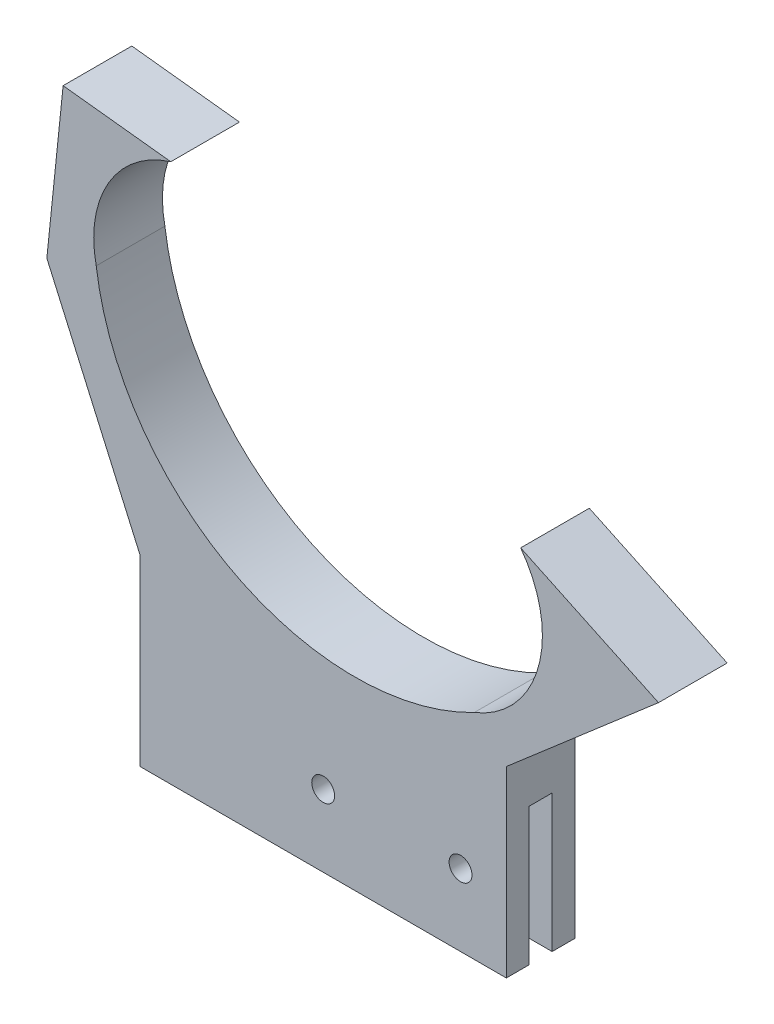
SolidWorks part; units mm, degrees
other "Markup1"
sketch "Sketch6" plane through (114.3, 38.1, 139.7) normal (0.0122, 0.8279, 0.5607) x (0.9984, -0.0412, 0.0392)
material "Balsa"
ref_plane "Front Plane" through (0, 0, 0) normal (0, 0, 1) x (1, 0, 0)
ref_plane "Top Plane" through (0, 0, 0) normal (0, 1, 0) x (1, 0, 0)
ref_plane "Right Plane" through (0, 0, 0) normal (1, 0, 0) x (0, 0, -1)
sketch "Sketch7" plane through (0, 0, 0) normal (0, 0, 1) x (1, 0, 0)
  line L1 (0, 0) -> (50.8, 0)
  line L2 (0, 0) -> (0, 19.05)
  line L3 (0, 19.05) -> (50.8, 19.05)
  line L4 (50.8, 0) -> (50.8, 19.05)
  circle A0 centre (25.4, 9.9757) radius 1.5875
  circle A1 centre (44.45, 9.9757) radius 1.5875
  point P9 (0, 0)
  dimension "Mount Diameter" = 3.175
  dimension "Mount Width" = 19.05
  dimension "Mount Length" = 50.8
  dimension "Basket Mount" = 19.05
  dimension "Mount Offset" = 6.35
extrude "Boss-Extrude1" add sketch "Sketch7" along normal mid plane 9.525 contours L3 L4 L1 L2 | A0 | A1
extrude "Cut-Extrude1" cut sketch "Sketch7<6>" against normal mid plane 3.175 contours L3 L4 L1 L2
sketch "Sketch7<6>" plane through (0, 0, 0) normal (0, 0, 1) x (1, 0, 0) same geometry as "Sketch7"
sketch "Sketch13" plane through (0, 0, 4.7625) normal (0, 0, 1) x (1, 0, 0)
  line L0 (0, 19.05) -> (50.8, 19.05)
  line L1 (0, 19.05) -> (0, 25.4)
  line L2 (50.8, 19.05) -> (50.8, 25.4)
  line L3 (0, 25.4) -> (50.8, 25.4)
  dimension "D1" = 6.35
extrude "Boss-Extrude4" add sketch "Sketch13" against normal blind 9.525
sketch "Sketch14" plane through (0, 0, 4.7625) normal (0, 0, 1) x (1, 0, 0)
  line L0 (50.8, 25.4) -> (71.9025, 43.6226)
  line L1 (71.9025, 43.6226) -> (52.7873, 52.6559)
  line L2 (0, 25.4) -> (-12.9266, 54.5938)
  line L4 (0, 25.4) -> (50.8, 25.4)
  line L5 (4.2644, 74.7738) -> (-10.6693, 76.4461)
  line L6 (-10.6693, 76.4461) -> (-12.9266, 54.5938)
  arc A0 (-6.0786, 57.1043) -> (46.3569, 29.6648) centre (29.7863, 61.8197) ccw
  arc A1 (46.3569, 29.6648) -> (52.7873, 52.6559) centre (40.7687, 43.6226) ccw
  arc A2 (-6.0786, 57.1043) -> (4.2644, 74.7738) centre (8.7052, 60.3125) cw
extrude "Boss-Extrude5" add sketch "Sketch14" against normal blind 9.525
equation "\"L1\"= 15in"
equation "\"L2\"= 12.5in"
equation "\"L3\"= 15.207in"
equation "\"L4\"= 15in"
equation "\"LL\"= 30in"
equation "\"w\"= 0.75in"
equation "\"t\"= 0.125in"
equation "\"holeD\" = 0.125in"
equation "\"holeOffset\" = 0.25in"
equation "\"basketMount\" = 0.75in"
equation "\"Mount Width@Sketch7\"= \"w\""
equation "\"Basket Mount@Sketch7\"= \"basketMount\""
equation "\"Mount Offset@Sketch7\"= \"holeOffset\""
equation "\"mountLength\" = 2in"
equation "\"Mount Length@Sketch7\"= \"mountLength\""
equation "\"Mount Diameter@Sketch7\"= \"holeD\""
